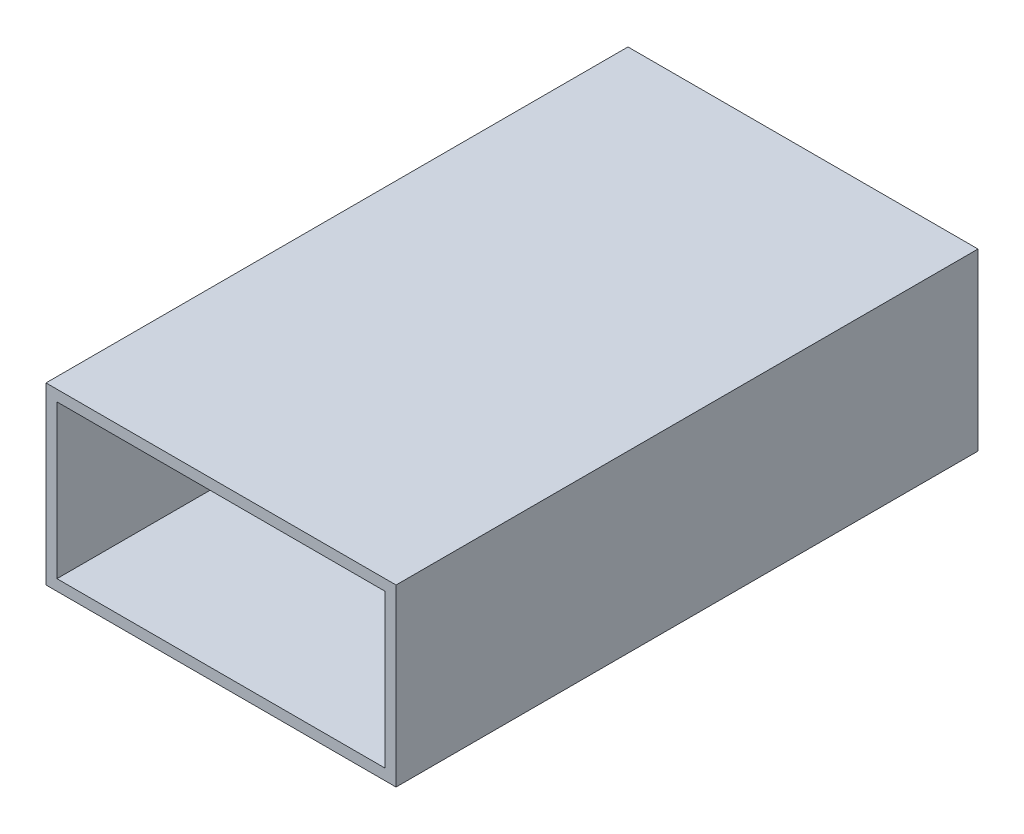
SolidWorks part; units mm, degrees
material "6061-T6 (SS)"
ref_plane "Front Plane" through (0, 0, 0) normal (0, 0, 1) x (1, 0, 0)
ref_plane "Top Plane" through (0, 0, 0) normal (0, 1, 0) x (1, 0, 0)
ref_plane "Right Plane" through (0, 0, 0) normal (1, 0, 0) x (0, 0, -1)
sketch "Sketch1" plane through (0, 0, 0) normal (0, 0, 1) x (1, 0, 0)
  line L1 (-25.4, -12.7) -> (25.4, -12.7)
  line L2 (-25.4, -12.7) -> (-25.4, 12.7)
  line L3 (-25.4, 12.7) -> (25.4, 12.7)
  line L4 (25.4, -12.7) -> (25.4, 12.7)
  line L5 (-25.4, -12.7) -> (25.4, 12.7) construction
  line L6 (-25.4, 12.7) -> (25.4, -12.7) construction
  line L7 (-23.8125, -11.1125) -> (23.8125, -11.1125)
  line L8 (-23.8125, -11.1125) -> (-23.8125, 11.1125)
  line L9 (-23.8125, 11.1125) -> (23.8125, 11.1125)
  line L10 (23.8125, -11.1125) -> (23.8125, 11.1125)
  line L11 (-23.8125, -11.1125) -> (23.8125, 11.1125) construction
  line L12 (-23.8125, 11.1125) -> (23.8125, -11.1125) construction
  point P0 (0, 0)
  point P6 (0, 0)
  dimension "D1" = 50.8
  dimension "D2" = 25.4
  dimension "D3" = 1.5875
  dimension "D4" = 1.5875
extrude "Boss-Extrude1" add sketch "Sketch1" along normal mid plane 84.455
